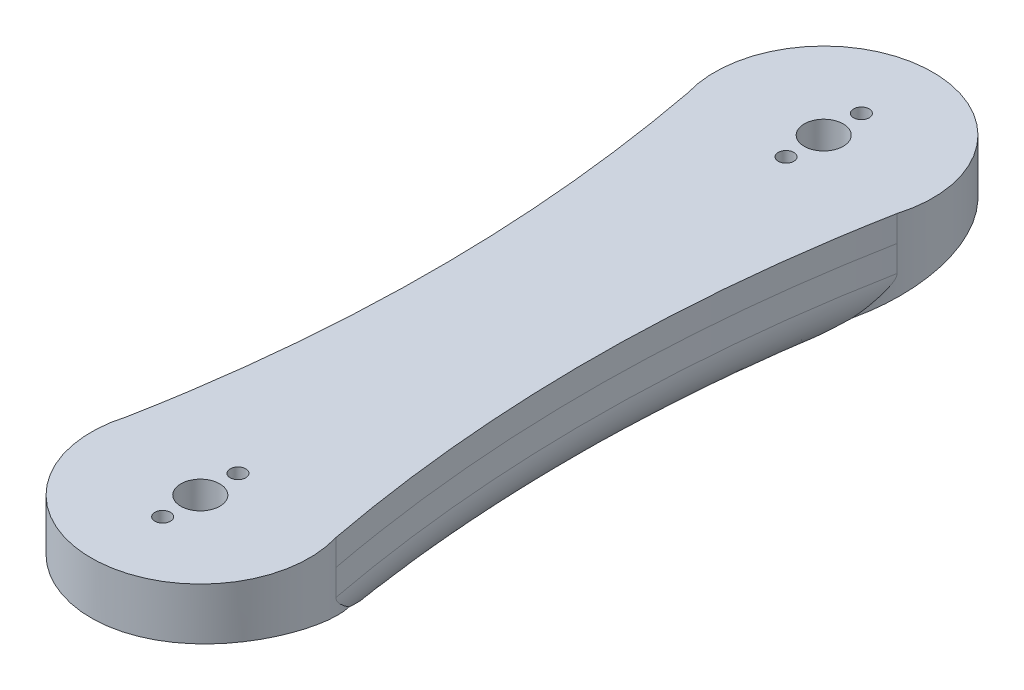
SolidWorks part; units mm, degrees
ref_plane "Front Plane" through (0, 0, 0) normal (0, 0, 1) x (1, 0, 0)
ref_plane "Top Plane" through (0, 0, 0) normal (0, 1, 0) x (1, 0, 0)
ref_plane "Right Plane" through (0, 0, 0) normal (1, 0, 0) x (0, 0, -1)
sketch "Sketch1" plane through (0, 0, 0) normal (0, 1, 0) x (1, 0, 0)
  line L0 (0, 0) -> (0, 120) construction
  line L1 (-20.1246, 6) -> (20.1246, 6) construction
  line L2 (-20.1246, 114) -> (20.1246, 114) construction
  circle A0 centre (0, 0) radius 21
  circle A1 centre (0, 120) radius 21
  spline S0 degree 2 poles (-20.1246, 114) (-9.8754, 60) (-20.1246, 6) knots 0 0 0 1 1 1
  spline S1 degree 2 poles (20.1246, 114) (9.8754, 60) (20.1246, 6) knots 0 0 0 1 1 1
  dimension "D1" = 42
  dimension "D2" = 120
  dimension "D3" = 6
  dimension "D4" = 6
  dimension "D5" = 60
  dimension "D6" = 15
extrude "Boss-Extrude1" add sketch "Sketch1" along normal blind 16 contours S1 A1 S0 A0 region at (0, 0, -60)
extrude "Boss-Extrude2" add sketch "Sketch1<3>" along normal blind 21 contours A0 | A1 region at (0, 0, 0) region at (0, 0, -120)
sketch "Sketch1<3>" plane through (0, 0, 0) normal (0, 1, 0) x (1, 0, 0) same geometry as "Sketch1"
sketch "Sketch2" plane through (0, 0, 0) normal (1, 0, 0) x (0, 0, -1)
  line L0 (-21, 0) -> (141, 0)
  line L1 (141, 0) -> (141, 11)
  line L2 (141, 0) -> (141, 21) construction
  line L3 (-21, 0) -> (-21, 11)
  line L4 (-21, 21) -> (-21, 0) construction
  spline S0 degree 3 poles (-21, 11) (-4.4357, 11.4952) (10.432, 8.6233) (21, 0) knots 0 0 0 0 1 1 1 1
  spline S1 degree 3 poles (141, 11) (122.195, 10.4425) (103.5451, 4.9983) (99, 0) knots 0 0 0 0 1 1 1 1
  dimension "D1" = 11
  dimension "D2" = 42
  dimension "D3" = 42
  dimension "D4" = 11
extrude "Cut-Extrude1" cut sketch "Sketch2" against normal through all both and the other way through all contours S0 L3 L0 | L1 S1 L0 region at (0, 4.6814, 4.2812) region at (0, 4.3874, -124.5212)
ref_plane "Plane1" through (0, 15, 0) normal (0, 1, 0) x (1, 0, 0)
fillet "Fillet1" radius 11 2 edges
sketch "Sketch3" plane through (0, 15, 0) normal (0, 1, 0) x (1, 0, 0)
  arc A2 (-20.1246, 114) -> (20.1246, 114) centre (0, 120) ccw
  arc A3 (20.1246, 6) -> (-20.1246, 6) centre (0, 0) ccw
  arc A4 (-20.1246, 114) -> (20.1246, 114) centre (0, 120) ccw
  arc A5 (20.1246, 6) -> (-20.1246, 6) centre (0, 0) ccw
  parabola Q2 (20.1246, 6) -> (20.1246, 114) focus (157.2547, 60) apex (15, 60)
  parabola Q3 (-20.1246, 114) -> (-20.1246, 6) focus (-157.2547, 60) apex (-15, 60)
  parabola Q4 (20.1246, 6) -> (20.1246, 114) focus (157.2547, 60) apex (15, 60)
  parabola Q5 (-20.1246, 114) -> (-20.1246, 6) focus (-157.2547, 60) apex (-15, 60)
  dimension "D1" = 0
extrude "Boss-Extrude3" add sketch "Sketch3" along normal up to surface (6 mm away) up to face at (0, 21, 21)
sketch "Sketch4" plane through (0, 0, 0) normal (0, 0, 1) x (1, 0, 0)
  circle A0 centre (0, 9) radius 5.75
  dimension "D1" = 11.5
  dimension "D2" = 9
extrude "Cut-Extrude2" cut sketch "Sketch4" against normal blind 131
sketch "Sketch5" plane through (0, 15, 0) normal (0, 1, 0) x (1, 0, 0)
  arc A8 (17.2497, 114.8571) -> (-17.2497, 114.8571) centre (0, 120) ccw
  circle A9 centre (0, 120) radius 18
  arc A11 (-17.2497, 5.1429) -> (17.2497, 5.1429) centre (0, 0) ccw
  circle A12 centre (0, 0) radius 18
  dimension "D1" = 3
  dimension "D2" = 3
extrude "Cut-Extrude3" cut sketch "Sketch5" against normal blind 131
sketch "Sketch6" plane through (0, 15, 0) normal (0, -1, 0) x (1, 0, 0)
  line L0 (0, -7.25) -> (0, 7.25) construction
  line L1 (0, 0) -> (0, -120) construction
  line L2 (0, -60) -> (-39.1708, -60)
  line L3 (0, -112.75) -> (0, -127.25) construction
  circle A0 centre (0, 0) radius 3.75
  circle A1 centre (0, -7.25) radius 1.5
  circle A2 centre (0, 7.25) radius 1.5
  circle A3 centre (0, -127.25) radius 1.5
  circle A4 centre (0, -112.75) radius 1.5
  circle A5 centre (0, -120) radius 3.75
  point P7 (0, 0)
  dimension "D1" = 7.5
  dimension "D2" = 3
  dimension "D3" = 7.25
extrude "Cut-Extrude4" cut sketch "Sketch6" against normal through all both and the other way through all contours A2 | A0 | A1 | A4 | A5 | A3 region at (0, 15, 0) region at (0, 15, -7.25) region at (0, 15, 7.25) region at (0, 15, -127.25) region at (0, 15, -112.75) region at (0, 15, -120)
